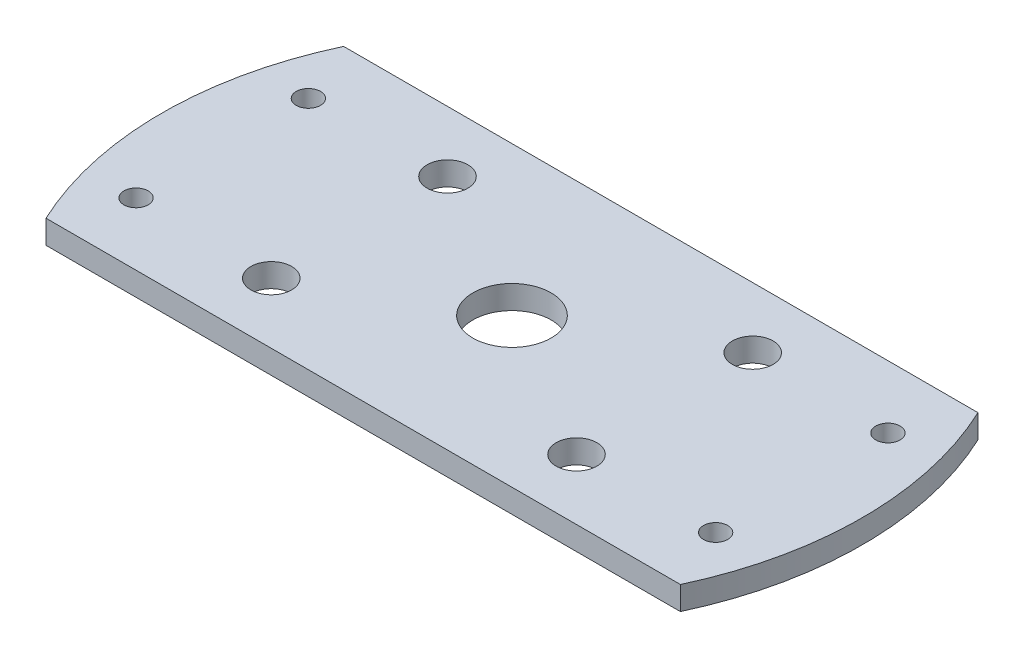
SolidWorks part; units mm, degrees
material "Thornel Mat VMA"
ref_plane "Front Plane" through (0, 0, 0) normal (0, 0, 1) x (1, 0, 0)
ref_plane "Top Plane" through (0, 0, 0) normal (0, 1, 0) x (1, 0, 0)
ref_plane "Right Plane" through (0, 0, 0) normal (1, 0, 0) x (0, 0, -1)
sketch "Sketch1" plane through (0, 0, 0) normal (0, 1, 0) x (1, 0, 0)
  line L0 (0, 0) -> (0, 56.5511) construction
  line L1 (0, 0) -> (118.6796, 0) construction
  line L2 (-62, 19) -> (62, 19)
  line L5 (-62, -19) -> (62, -19)
  line L6 (62, 19) -> (62, 13)
  line L7 (62, 13) -> (59, 13)
  line L8 (59, 13) -> (59, -13)
  line L9 (62, -13) -> (59, -13)
  line L10 (62, -19) -> (62, -13)
  line L11 (-62, -19) -> (-62, -13)
  line L12 (-62, -13) -> (-59, -13)
  line L13 (-59, 13) -> (-59, -13)
  line L14 (-62, 13) -> (-59, 13)
  line L15 (-62, 19) -> (-62, 13)
  circle A0 centre (37, 11) radius 1.55
  circle A1 centre (-37, 11) radius 1.55
  circle A2 centre (-37, -11) radius 1.55
  circle A3 centre (37, -11) radius 1.55
  circle A4 centre (0, 0) radius 5
  circle A5 centre (20, 0) radius 1.55 construction
  circle A6 centre (-20, 0) radius 1.55 construction
  circle A7 centre (35, 0) radius 6 construction
  circle A8 centre (-35, 0) radius 6 construction
  circle A9 centre (28.5, 9) radius 1.55 construction
  circle A10 centre (28.5, -9) radius 1.55 construction
  circle A11 centre (-28.5, -9) radius 1.55 construction
  circle A12 centre (-28.5, 9) radius 1.55 construction
  point P13 (0, 19)
  point P18 (-61, 0)
  point P19 (61, 0)
  point P28 (59, 0)
  dimension "D1" = 3.1
  dimension "D2" = 22
  dimension "D3" = 8
  dimension "D4" = 3.1
  dimension "D5" = 10
  dimension "D6" = 20
  dimension "D11" = 35
  dimension "D12" = 12
  dimension "D13" = 8.5
  dimension "D14" = 2
  dimension "D7" = 38
  dimension "D8" = 124
  dimension "D9" = 3
  dimension "D10" = 6
extrude "Boss-Extrude1" add sketch "Sketch1" along normal blind 3
fillet "Fillet1" radius 3 8 edges at (-62, 1.5, -19) (-62, 1.5, -13) (-62, 1.5, 13) (-62, 1.5, 19) (62, 1.5, 19) (62, 1.5, 13) (62, 1.5, -13) (62, 1.5, -19)
sketch "草图2" plane through (0, 3, 0) normal (0, 1, 0) x (1, 0, 0)
  line L0 (0, 19) -> (0, -19) construction
  line L1 (59, 19) -> (-59, 19) construction
  line L2 (-59, -19) -> (59, -19) construction
  line L3 (0, 0) -> (-21.55, 0) construction
  circle A0 centre (-20, 0) radius 1.55 construction
sketch "草图3" plane through (0, 0, 0) normal (0, -1, 0) x (1, 0, 0)
  circle A0 centre (-30.75, -15) radius 2.1 construction
  circle A1 centre (-30.75, -15) radius 2.1
  circle A2 centre (-30.75, 15) radius 2.1 construction
  circle A3 centre (-30.75, 15) radius 2.1
sketch "草图4" plane through (0, 0, 0) normal (0, -1, 0) x (1, 0, 0)
  line L0 (0, 0) -> (0, 63.4958) construction
  line L1 (-45, 19) -> (-45, -19)
  line L2 (-59, 19) -> (59, 19) construction
  line L3 (59, -19) -> (-59, -19) construction
  line L4 (-45, -19) -> (-67.4332, -19)
  line L5 (-67.4332, -19) -> (-67.4332, 19)
  line L6 (-67.4332, 19) -> (-45, 19)
  line L7 (67.4332, 19) -> (45, 19)
  line L8 (67.4332, -19) -> (67.4332, 19)
  line L9 (45, -19) -> (67.4332, -19)
  line L10 (45, 19) -> (45, -19)
  dimension "D1" = 45
extrude "切除-拉伸1" cut sketch "草图4" against normal blind 10
sketch "草图6" plane through (0, 3, 0) normal (0, 1, 0) x (1, 0, 0)
  line L1 (45, 19) -> (-45, 19) construction
  line L2 (-45, -19) -> (45, -19) construction
  line L3 (-40.5, -19) -> (-45, -19)
  line L4 (-45, -19) -> (-45, 19)
  line L5 (-45, 19) -> (-40.5, 19)
  line L6 (0, 0) -> (0, 31.3174) construction
  line L7 (45, 19) -> (40.5, 19)
  line L8 (45, -19) -> (45, 19)
  line L9 (40.5, -19) -> (45, -19)
  circle A0 centre (0, 0) radius 44.7353 construction
  arc A1 (-40.5, 19) -> (-40.5, -19) centre (0, 0) ccw
  arc A2 (40.5, 19) -> (40.5, -19) centre (0, 0) cw
extrude "切除-拉伸2" cut sketch "草图6" against normal blind 10
sketch "草图7" plane through (0, 0, 0) normal (0, -1, 0) x (1, 0, 0)
  line L0 (0, 0) -> (0, -31.3174) construction
  circle A0 centre (0, -22.5) radius 2.6
  circle A1 centre (-19.4856, -11.25) radius 2.6
  circle A2 centre (-19.4856, 11.25) radius 2.6
  circle A3 centre (0, 22.5) radius 2.6
  circle A4 centre (19.4856, 11.25) radius 2.6
  circle A5 centre (19.4856, -11.25) radius 2.6
  point P18 (0, 0)
  dimension "D3" = 5.2
  dimension "D1" = 22.5
  dimension "D2" = 6
extrude "切除-拉伸3" cut sketch "草图7" against normal blind 10
